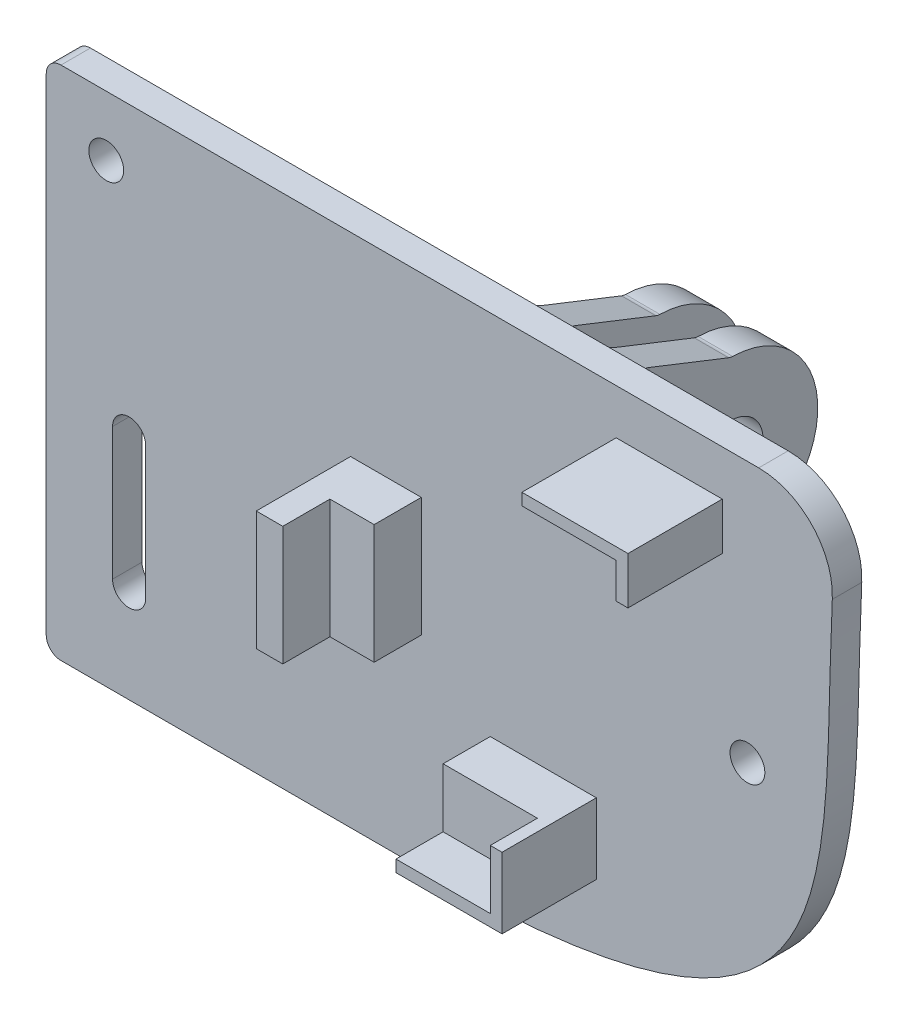
SolidWorks part; units mm, degrees
ref_plane "Front Plane" through (0, 0, 0) normal (0, 0, 1) x (1, 0, 0)
ref_plane "Top Plane" through (0, 0, 0) normal (0, 1, 0) x (1, 0, 0)
ref_plane "Right Plane" through (0, 0, 0) normal (1, 0, 0) x (0, 0, -1)
sketch "Sketch3" plane through (0, 0, 48.1769) normal (0, 0, -1) x (-1, 0, 0)
  line L0 (-5.3306, -70.9645) -> (-5.3306, -26.5145)
  line L1 (-5.3306, -26.5145) -> (-73.555, -26.5145)
  line L2 (-5.3306, -70.9645) -> (-37.0806, -70.9645)
  line L3 (-65.9591, -70.9645) -> (9.5752, -70.9645) construction
  spline S0 degree 3 poles (-37.0806, -70.9645) (-79.6375, -70.9645) (-70.893, -52.6762) (-73.555, -26.5145) knots 0 0 0 0 1 1 1 1
  dimension "D1" = 44.45
  dimension "D2" = 68.2244
  dimension "D3" = 31.75
extrude "Boss-Extrude1" add sketch "Sketch3" along normal blind 2.54
ref_plane "Plane2" through (45.9706, 0, 0) normal (-1, 0, 0) x (0, 0, 1)
sketch "Sketch8" plane through (45.9706, 0, 0) normal (-1, 0, 0) x (0, 0, 1)
  line L0 (45.6369, -70.9645) -> (45.6369, -26.5145) construction
  line L1 (18.8044, -37.5827) -> (45.6369, -37.5827) construction
  line L3 (45.6369, -70.9645) -> (45.6369, -26.5145) construction
  line L6 (45.6369, -45.0884) -> (45.6369, -30.077)
  line L7 (37.5851, -30.077) -> (45.6369, -26.902)
  line L8 (45.6369, -26.902) -> (45.6369, -30.077)
  line L9 (37.5851, -45.0884) -> (45.6369, -48.2634)
  line L10 (45.6369, -48.2634) -> (45.6369, -45.0884)
  circle A0 centre (37.5851, -37.5827) radius 2.794
  arc A1 (37.5851, -30.077) -> (37.5851, -45.0884) centre (37.5851, -37.5827) ccw
  dimension "D1" = 5.588
  dimension "D2" = 15.0114
  dimension "D3" = 8.0518
  dimension "D4" = 3.175
  dimension "D5" = 3.175
extrude "Boss-Extrude5" add sketch "Sketch8" along normal mid plane 2.9718
ref_plane "Plane3" through (52.2444, 0, 0) normal (-1, 0, 0) x (0, 0, 1)
sketch "Sketch9" plane through (52.2444, 0, 0) normal (-1, 0, 0) x (0, 0, 1)
  line L1 (37.5851, -30.077) -> (45.6369, -26.902)
  line L3 (45.6369, -70.9645) -> (45.6369, -26.5145) construction
  line L4 (45.6369, -30.077) -> (45.6369, -45.0884)
  line L6 (45.6369, -26.902) -> (45.6369, -30.077)
  line L7 (37.5851, -45.0884) -> (45.6369, -48.2634)
  line L8 (45.6369, -26.5145) -> (45.6369, -70.9645) construction
  line L9 (45.6369, -48.2634) -> (45.6369, -45.0884)
  circle A1 centre (37.5851, -37.5827) radius 2.794
  arc A2 (37.5851, -30.077) -> (37.5851, -45.0884) centre (37.5851, -37.5827) ccw
  dimension "D2" = 5.588
  dimension "D1" = 3.175
extrude "Boss-Extrude6" add sketch "Sketch9" along normal mid plane 2.9718
fillet "Fillet1" radius 6.35 1 edges at (73.555, -26.5145, 46.9069)
fillet "Fillet2" radius 1.27 2 edges at (5.3306, -70.9645, 46.9069) (5.3306, -26.5145, 46.9069)
sketch "Sketch11" plane through (0, 0, 48.1769) normal (0, 0, 1) x (1, 0, 0)
  circle A0 centre (10.502, -31.6859) radius 1.5
  circle A1 centre (65.7642, -49.0033) radius 1.5
extrude "Cut-Extrude1" cut sketch "Sketch11" against normal through all
sketch "Sketch13" plane through (0, 0, 48.1769) normal (0, 0, 1) x (1, 0, 0)
  line L0 (12.4736, -62.6668) -> (12.4736, -51.2712) construction
  line L1 (11.0456, -62.6668) -> (11.0456, -51.2712)
  line L2 (13.9016, -62.6668) -> (13.9016, -51.2712)
  line L3 (5.3306, -69.6945) -> (5.3306, -27.7845) construction
  arc A0 (11.0456, -62.6668) -> (13.9016, -62.6668) centre (12.4736, -62.6668) ccw
  arc A1 (13.9016, -51.2712) -> (11.0456, -51.2712) centre (12.4736, -51.2712) ccw
  point P2 (12.4736, -56.969)
  dimension "D1" = 5.715
extrude "Cut-Extrude3" cut sketch "Sketch13" against normal through all
ref_axis "Axis1" through (12.4736, -51.2712, 45.6369) along (0, 0, 1)
ref_axis "Axis2" through (12.4736, -62.6668, 45.6369) along (0, 0, 1)
sketch "Sketch14" plane through (0, 0, 48.1769) normal (0, 0, 1) x (1, 0, 0)
  line L1 (43.5987, -58.1375) -> (52.7427, -58.1375)
  line L2 (43.5987, -58.1375) -> (43.5987, -64.2335)
  line L3 (43.5987, -64.2335) -> (52.7427, -64.2335)
  line L4 (52.7427, -58.1375) -> (52.7427, -64.2335)
  line L9 (31.5597, -43.2573) -> (37.6557, -43.2573)
  line L10 (31.5597, -43.2573) -> (31.5597, -53.5348)
  line L11 (31.5597, -53.5348) -> (37.6557, -53.5348)
  line L12 (37.6557, -43.2573) -> (37.6557, -53.5348)
  line L13 (54.4528, -30.414) -> (63.5968, -30.414)
  line L14 (54.4528, -30.414) -> (54.4528, -34.478)
  line L15 (54.4528, -34.478) -> (63.5968, -34.478)
  line L16 (63.5968, -30.414) -> (63.5968, -34.478)
  line L18 (34.0997, -62.9635) -> (34.0997, -31.684) construction
  line L19 (34.0997, -31.684) -> (62.3268, -31.684) construction
  line L20 (62.3268, -31.684) -> (62.3268, -42.4101) construction
  line L21 (51.4727, -42.4101) -> (51.4727, -62.9635) construction
  line L22 (51.4727, -62.9635) -> (34.0997, -62.9635) construction
  dimension "D1" = 1.27
  dimension "D2" = 1.27
  dimension "D3" = 4.064
  dimension "D4" = 2.794
  dimension "D5" = 6.096
  dimension "D6" = 2.54
  dimension "D7" = 1.27
  dimension "D8" = 9.144
  dimension "D9" = 9.144
  dimension "D10" = 6.096
extrude "Boss-Extrude7" add sketch "Sketch14" along normal blind 4.064
sketch "Sketch15" plane through (0, 0, 52.2409) normal (0, 0, 1) x (1, 0, 0)
  line L0 (31.5597, -53.5348) -> (37.6557, -53.5348) construction
  line L1 (31.5597, -43.2573) -> (33.8457, -43.2573)
  line L2 (31.5597, -43.2573) -> (31.5597, -53.5348)
  line L3 (31.5597, -53.5348) -> (33.8457, -53.5348)
  line L4 (33.8457, -43.2573) -> (33.8457, -53.5348)
  line L5 (54.4528, -30.414) -> (54.4528, -31.43)
  line L6 (54.4528, -30.414) -> (54.4528, -34.478) construction
  line L7 (54.4528, -31.43) -> (62.5808, -31.43)
  line L8 (62.5808, -31.43) -> (62.5808, -34.478)
  line L9 (54.4528, -34.478) -> (63.5968, -34.478) construction
  line L10 (62.5808, -34.478) -> (63.5968, -34.478)
  line L11 (63.5968, -34.478) -> (63.5968, -30.414)
  line L12 (63.5968, -30.414) -> (54.4528, -30.414)
  line L13 (43.5987, -63.2175) -> (51.7267, -63.2175)
  line L14 (43.5987, -58.1375) -> (43.5987, -64.2335) construction
  line L15 (51.7267, -63.2175) -> (51.7267, -58.1375)
  line L16 (52.7427, -58.1375) -> (43.5987, -58.1375) construction
  line L17 (51.7267, -58.1375) -> (52.7427, -58.1375)
  line L18 (52.7427, -58.1375) -> (52.7427, -64.2335)
  line L19 (52.7427, -64.2335) -> (43.5987, -64.2335)
  line L20 (43.5987, -64.2335) -> (43.5987, -63.2175)
  line L21 (34.0997, -31.684) -> (62.3268, -31.684) construction
  line L22 (62.3268, -31.684) -> (62.3268, -42.4101) construction
  line L23 (51.4727, -42.4101) -> (51.4727, -62.9635) construction
  line L24 (51.4727, -62.9635) -> (34.0997, -62.9635) construction
  line L25 (34.0997, -62.9635) -> (34.0997, -31.684) construction
  dimension "D1" = 0.254
  dimension "D2" = 0.254
  dimension "D3" = 0.254
  dimension "D4" = 0.254
  dimension "D5" = 0.254
extrude "Boss-Extrude8" add sketch "Sketch15" along normal blind 4.064
fillet "Fillet3" radius 1 12 edges at (45.9706, -30.077, 37.5851) (52.2444, -30.077, 37.5851) (45.9706, -45.0884, 37.5851) (52.2444, -45.0884, 37.5851) (52.2444, -26.902, 45.6369) (45.9706, -26.902, 45.6369) (50.7585, -37.5827, 45.6369) (53.7303, -37.5827, 45.6369) (52.2444, -48.2634, 45.6369) (47.4565, -37.5827, 45.6369) (44.4847, -37.5827, 45.6369) (45.9706, -48.2634, 45.6369)
